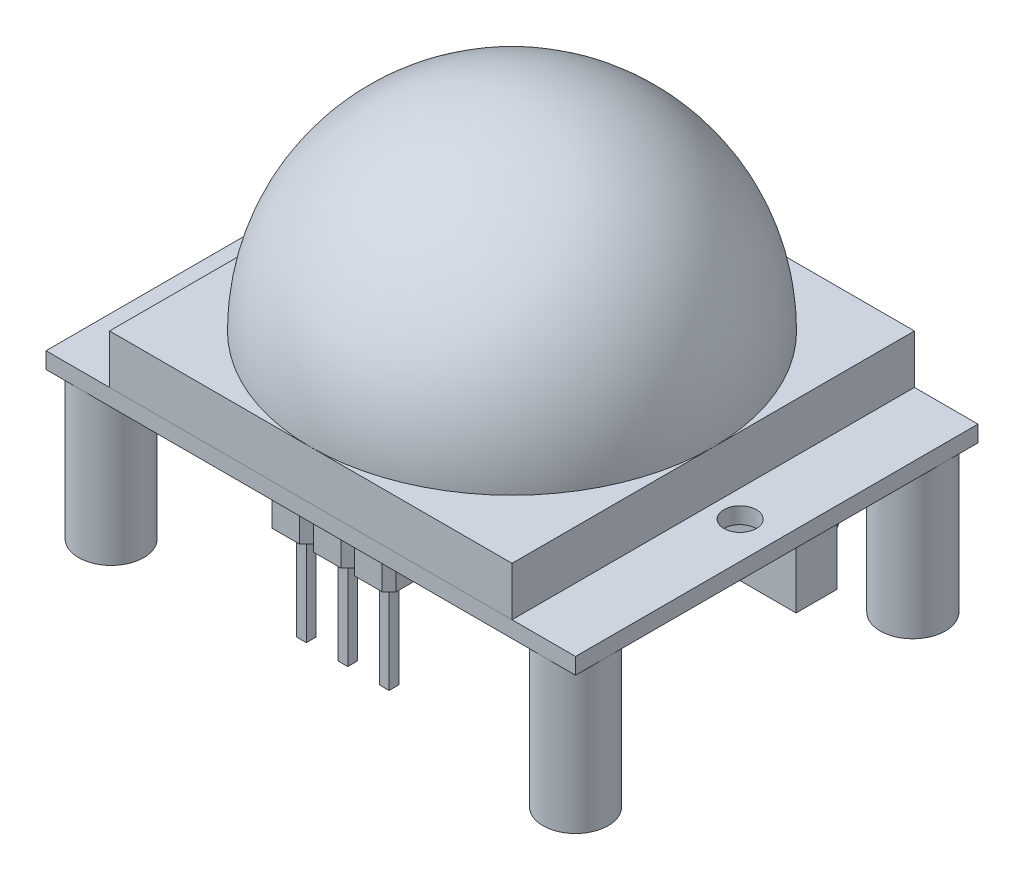
SolidWorks part; units mm, degrees
other "PCB"
other "Diffuser"
ref_plane "Alzado" through (0, 0, 0) normal (0, 0, 1) x (1, 0, 0)
ref_plane "Planta" through (0, 0, 0) normal (0, 1, 0) x (1, 0, 0)
ref_plane "Vista lateral" through (0, 0, 0) normal (1, 0, 0) x (0, 0, -1)
sketch "Croquis1" plane through (0, 0, 0) normal (0, 1, 0) x (1, 0, 0)
  line L0 (-16.25, 12.35) -> (16.25, -12.35) construction
  line L1 (-16.25, 12.35) -> (16.25, 12.35)
  line L2 (-16.25, 12.35) -> (-16.25, -12.35)
  line L3 (-16.25, -12.35) -> (16.25, -12.35)
  line L4 (16.25, 12.35) -> (16.25, -12.35)
  dimension "D1" = 32.5
  dimension "D2" = 24.7
extrude "Saliente-Extruir1" add sketch "Croquis1" along normal blind 1
sketch "Croquis2" plane through (0, 1, 0) normal (0, 1, 0) x (1, 0, 0)
  line L0 (16.25, 12.35) -> (-16.25, 12.35) construction
  line L1 (-12.35, 12.35) -> (12.35, 12.35)
  line L2 (-12.35, 12.35) -> (-12.35, -12.35)
  line L3 (-12.35, -12.35) -> (12.35, -12.35)
  line L4 (12.35, 12.35) -> (12.35, -12.35)
  line L5 (-16.25, -12.35) -> (16.25, -12.35) construction
  line L6 (-12.35, 12.35) -> (12.35, -12.35) construction
extrude "Saliente-Extruir2" add sketch "Croquis2" along normal blind 3 separate body
sketch "Croquis3" plane through (0, 0, 0) normal (0, 0, 1) x (1, 0, 0)
  line L0 (12.35, 4) -> (12.35, 1) construction
  line L1 (-12.35, 4) -> (12.35, 4) construction
  line L2 (0, 16.35) -> (0, 4)
  line L3 (0, 4) -> (12.35, 4)
  arc A0 (0, 16.35) -> (12.35, 4) centre (0, 4) cw
revolve "Revolución1" add sketch "Croquis3" angle 360 about L2
sketch "Croquis4" plane through (0, 1, 0) normal (0, 1, 0) x (1, 0, 0)
  line L0 (0, 12.35) -> (0, 0) construction
  line L1 (-16.25, 12.35) -> (-16.25, -12.35) construction
  line L2 (-14, 0) -> (-16.25, 0) construction
  circle A0 centre (-14, 0) radius 1
  arc A1 (0, 12.35) -> (-12.35, 0) centre (0, 0) ccw construction
  circle A2 centre (14, 0) radius 1
  dimension "D1" = 2
  dimension "D2" = 28
extrude "Cortar-Extruir1" cut sketch "Croquis4" against normal up to next (1 mm away) contours A2 | A0 region at (14, 1, 0)
sketch "Croquis5" plane through (0, 0, 0) normal (0, -1, 0) x (1, 0, 0)
  line L0 (-16.25, 12.35) -> (16.25, 12.35) construction
  line L1 (-16.25, -12.35) -> (-16.25, 12.35) construction
  line L2 (16.25, 12.35) -> (16.25, -12.35) construction
  line L3 (16.25, -12.35) -> (-16.25, -12.35) construction
  circle A0 centre (-14.25, 10.35) radius 2
  circle A1 centre (14.25, 10.35) radius 2
  circle A2 centre (14.25, -10.35) radius 2
  circle A3 centre (-6.75, -10.35) radius 2
  dimension "D1" = 4
  dimension "D2" = 21
extrude "Saliente-Extruir3" add sketch "Croquis5" along normal blind 9 separate body
sketch "Croquis6" plane through (0, 0, 0) normal (0, -1, 0) x (1, 0, 0)
  line L1 (-3.2906, -6.7277) -> (3.2094, -6.7277)
  line L2 (-3.2906, -6.7277) -> (-3.2906, -9.2277)
  line L3 (-3.2906, -9.2277) -> (3.2094, -9.2277)
  line L4 (3.2094, -6.7277) -> (3.2094, -9.2277)
  line L5 (4.2094, -6.7277) -> (10.7094, -6.7277)
  line L6 (4.2094, -6.7277) -> (4.2094, -9.2277)
  line L7 (4.2094, -9.2277) -> (10.7094, -9.2277)
  line L8 (10.7094, -6.7277) -> (10.7094, -9.2277)
  dimension "D1" = 14
  dimension "D2" = 1
  dimension "D3" = 2.5
extrude "Saliente-Extruir4" add sketch "Croquis6" along normal up to surface (9 mm away) separate body up to face at (-6.75, -9, -12.35)
sketch "Croquis8" plane through (0, 0, -9.2277) normal (0, 0, -1) x (-1, 0, 0)
  line L0 (-7.4594, -5.656) -> (-7.4594, -9) construction
  line L1 (-4.2094, -9) -> (-10.7094, -9) construction
  line L2 (0.0406, -9) -> (0.0406, -5.656) construction
  line L3 (3.2906, -9) -> (-3.2094, -9) construction
  circle A0 centre (-7.4594, -5.656) radius 2.5
  circle A1 centre (0.0406, -5.656) radius 2.5
  dimension "D1" = 5
extrude "Saliente-Extruir5" add sketch "Croquis8" along normal blind 1 separate body
sketch "Croquis9" plane through (0, 0, 0) normal (0, -1, 0) x (1, 0, 0)
  line L0 (-3.3857, 11.35) -> (-1.6943, 11.35)
  line L1 (-1.6943, 11.35) -> (-1.27, 10.9257)
  line L2 (-1.27, 10.9257) -> (-0.8457, 11.35)
  line L3 (-0.8457, 11.35) -> (0.8457, 11.35)
  line L4 (0.8457, 11.35) -> (1.27, 10.9257)
  line L5 (1.27, 10.9257) -> (1.6943, 11.35)
  line L6 (1.6943, 11.35) -> (3.3857, 11.35)
  line L7 (3.3857, 11.35) -> (3.81, 10.9257)
  line L8 (3.81, 10.9257) -> (3.81, 9.2343)
  line L9 (3.81, 9.2343) -> (3.3857, 8.81)
  line L10 (3.3857, 8.81) -> (1.6943, 8.81)
  line L11 (1.6943, 8.81) -> (1.27, 9.2343)
  line L12 (1.27, 9.2343) -> (0.8457, 8.81)
  line L13 (0.8457, 8.81) -> (-0.8457, 8.81)
  line L14 (-0.8457, 8.81) -> (-1.27, 9.2343)
  line L15 (-1.27, 9.2343) -> (-1.6943, 8.81)
  line L16 (-1.6943, 8.81) -> (-3.3857, 8.81)
  line L17 (-3.3857, 8.81) -> (-3.81, 9.2343)
  line L18 (-3.81, 9.2343) -> (-3.81, 10.9257)
  line L19 (-3.81, 10.9257) -> (-3.3857, 11.35)
  line L20 (0, 11.35) -> (0, 12.35) construction
  line L22 (-16.25, 12.35) -> (16.25, 12.35) construction
  dimension "D1" = 7.62
  dimension "D2" = 1
  dimension "D3" = 0.6
extrude "Saliente-Extruir6" add sketch "Croquis9" along normal blind 2.5 separate body
sketch "Croquis10" plane through (0, -2.5, 0) normal (0, -1, 0) x (1, 0, 0)
  line L0 (-2.54, 11.35) -> (-2.54, 10.38)
  line L1 (-2.84, 10.38) -> (-2.24, 10.38)
  line L2 (-2.84, 10.38) -> (-2.84, 9.78)
  line L3 (-2.84, 9.78) -> (-2.24, 9.78)
  line L4 (-2.24, 10.38) -> (-2.24, 9.78)
  line L5 (-0.3, 10.38) -> (0.3, 10.38)
  line L6 (0.3, 10.38) -> (0.3, 9.78)
  line L7 (-0.3, 10.38) -> (-0.3, 9.78)
  line L8 (-0.3, 9.78) -> (0.3, 9.78)
  line L9 (-1.6943, 11.35) -> (-3.3857, 11.35) construction
  line L10 (-2.84, 10.08) -> (-3.81, 10.08)
  line L11 (-3.81, 10.9257) -> (-3.81, 9.2343) construction
  line L12 (2.24, 10.38) -> (2.84, 10.38)
  line L13 (2.84, 10.38) -> (2.84, 9.78)
  line L14 (2.24, 10.38) -> (2.24, 9.78)
  line L15 (2.24, 9.78) -> (2.84, 9.78)
  line L16 (-2.84, 10.38) -> (-2.24, 9.78) construction
  line L17 (-2.54, 10.08) -> (0, 10.08) construction
  line L19 (-0.3, 10.38) -> (0.3, 9.78) construction
  dimension "D1" = 0.6
  dimension "D3" = 2.54
  dimension "D2" = 3
extrude "Saliente-Extruir7" add sketch "Croquis10" along normal blind 6 contours L4 L1 L2 L3 | L7 L8 L6 L5 | L14 L15 L13 L12 region at (-2.54, -2.5, 10.08) region at (0, -2.5, 10.08) region at (2.54, -2.5, 10.08)
